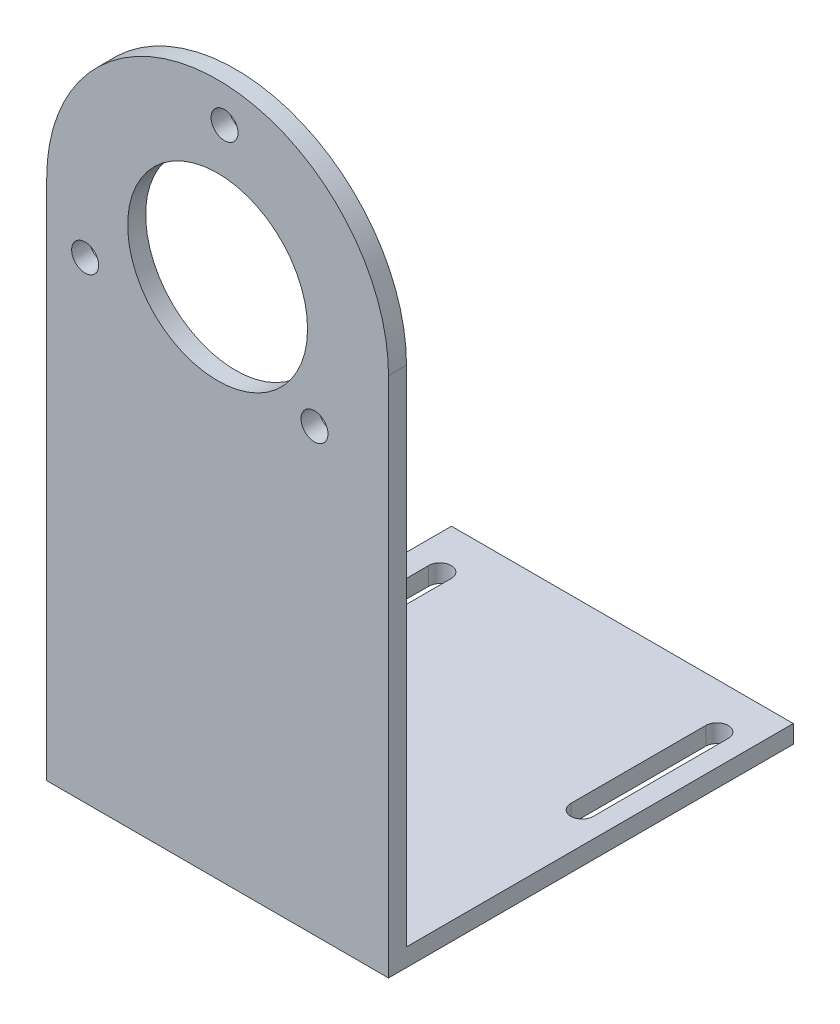
SolidWorks part; units mm, degrees
note: The reader was unsure of these and kept them because the rebuilt part matched: shared geometry of "Sketch3<4>".
ref_plane "Front Plane" through (0, 0, 0) normal (0, 0, 1) x (1, 0, 0)
ref_plane "Top Plane" through (0, 0, 0) normal (0, 1, 0) x (1, 0, 0)
ref_plane "Right Plane" through (0, 0, 0) normal (1, 0, 0) x (0, 0, -1)
sketch "Sketch1" plane through (0, 0, 0) normal (0, 1, 0) x (1, 0, 0)
  line L1 (-31.7703, 20.5518) -> (6.2297, 20.5518)
  line L2 (-31.7703, 20.5518) -> (-31.7703, -24.4482)
  line L3 (-31.7703, -24.4482) -> (6.2297, -24.4482)
  line L4 (6.2297, 20.5518) -> (6.2297, -24.4482)
  dimension "D1" = 38
  dimension "D2" = 45
extrude "Boss-Extrude1" add sketch "Sketch1" along normal blind 2
sketch "Sketch3" plane through (0, 0, 24.4482) normal (0, 0, 1) x (1, 0, 0)
  line L0 (-12.7703, 2) -> (-12.7703, 58)
  line L1 (-31.7703, 2) -> (6.2297, 2) construction
  line L2 (6.2297, 58) -> (6.2297, 2)
  line L3 (6.2297, 2) -> (6.2297, 0) construction
  line L4 (-31.7703, 58) -> (-31.7703, 2)
  circle A0 centre (-12.7703, 58) radius 19
  circle A2 centre (-12.7703, 58) radius 10
  dimension "D2" = 38
  dimension "D3" = 20
  dimension "D1" = 56
extrude "Boss-Extrude2" add sketch "Sketch3" against normal blind 2 separate body
extrude "Boss-Extrude3" add sketch "Sketch3<4>" against normal blind 2
sketch "Sketch3<4>" plane through (0, 0, 24.4482) normal (0, 0, 1) x (1, 0, 0) same geometry as "Sketch3"
sketch "Sketch4" plane through (0, 2, 0) normal (0, 1, 0) x (1, 0, 0)
  line L0 (2.8, 0.5) -> (2.8, 15.5) construction
  line L1 (1.55, 0.5) -> (1.55, 15.5)
  line L2 (4.05, 0.5) -> (4.05, 15.5)
  line L3 (-28, 0.5) -> (-28, 15.5) construction
  line L4 (-29.25, 0.5) -> (-29.25, 15.5)
  line L5 (-26.75, 0.5) -> (-26.75, 15.5)
  line L6 (-28, 8) -> (2.8, 8) construction
  arc A0 (1.55, 0.5) -> (4.05, 0.5) centre (2.8, 0.5) ccw
  arc A1 (4.05, 15.5) -> (1.55, 15.5) centre (2.8, 15.5) ccw
  arc A2 (-29.25, 0.5) -> (-26.75, 0.5) centre (-28, 0.5) ccw
  arc A3 (-26.75, 15.5) -> (-29.25, 15.5) centre (-28, 15.5) ccw
  point P2 (2.8, 8)
  point P10 (-28, 8)
  dimension "D1" = 30.8
extrude "Cut-Extrude1" cut sketch "Sketch4" against normal blind 2
sketch "Sketch6" plane through (0, 0, 24.4482) normal (0, 0, 1) x (1, 0, 0)
  circle A1 centre (-12, 73) radius 1.5
  circle A2 centre (-2, 49) radius 1.5
  circle A3 centre (-27.5, 52.5) radius 1.5
extrude "Cut-Extrude2" cut sketch "Sketch6" against normal blind 2
